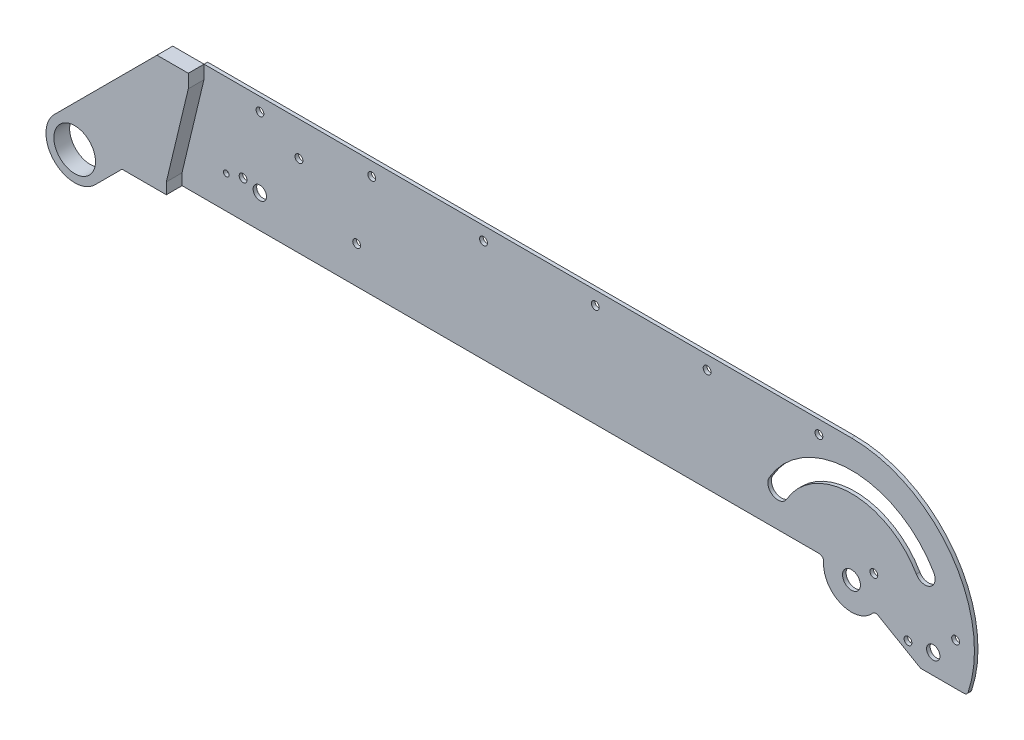
SolidWorks part; units mm, degrees
material "6061-T6 (SS)"
ref_plane "Front Plane" through (0, 0, 0) normal (0, 0, 1) x (1, 0, 0)
ref_plane "Top Plane" through (0, 0, 0) normal (0, 1, 0) x (1, 0, 0)
ref_plane "Right Plane" through (0, 0, 0) normal (1, 0, 0) x (0, 0, -1)
sketch "Sketch1" plane through (0, 0, 0) normal (0, 0, 1) x (1, 0, 0)
  line L0 (0, 0) -> (340.4001, 0) construction
  line L1 (340.4001, 0) -> (373.3091, 19) construction
  line L2 (340.4001, 0) -> (307.4911, 19) construction
  line L3 (340.4001, 0) -> (376.9688, -9.7841) construction
  line L5 (-50, -75) -> (450, -75)
  line L6 (-50, -75) -> (-50, 75)
  line L7 (-50, 75) -> (450, 75)
  line L8 (450, -75) -> (450, 75)
  circle A0 centre (0, 0) radius 9.3
  circle A1 centre (340.4001, 0) radius 4
  circle A2 centre (373.3091, 19) radius 4.5
  circle A3 centre (307.4911, 19) radius 4.5
  circle A4 centre (376.9688, -9.7841) radius 3
  circle A5 centre (340.4001, 0) radius 42.5
  circle A6 centre (340.4001, 0) radius 33.5
  dimension "D1" = 340.4001
  dimension "D2" = 36.5687
  dimension "D6" = 8
  dimension "D7" = 6
  dimension "D8" = 9
  dimension "D9" = 9
  dimension "D12" = 18.6
  dimension "D3" = 9.7841
  dimension "D4" = 150
  dimension "D5" = 120
  dimension "D10" = 38
  dimension "D11" = 38
  dimension "D13" = 150
  dimension "D14" = 500
  dimension "D15" = 75
  dimension "D16" = 50
extrude "Boss-Extrude1" add sketch "Sketch1" along normal blind 1.5875 contours L5 L8 L7 L6 A5 A0 | A6 A3 A5 A2 A4 | A6 A1 region at (189.2496, 0, 0) region at (377.7584, 20.1922, 0) region at (371.8434, 8.4252, 0)
sketch "Sketch3" plane through (0, 0, 1.5875) normal (0, 0, 1) x (1, 0, 0)
  line L0 (-50, 55) -> (450, 55)
  line L1 (340.4001, 0) -> (350.803, -6.9303) construction
  line L2 (-50, -75) -> (-50, 75) construction
  line L3 (450, -75) -> (450, 75) construction
  line L4 (-9.0863, 9.0863) -> (36.8274, 55)
  line L5 (0, 0) -> (-9.0863, 9.0863) construction
  line L6 (0, 0) -> (9.0863, -9.0863) construction
  line L7 (-50, 3) -> (450, 3) construction
  line L8 (9.0863, -9.0863) -> (21.1726, 3)
  line L9 (30.8962, 3) -> (328.2654, 3)
  line L10 (450, -18.7841) -> (-50, -18.7841) construction
  line L11 (350.803, -6.9303) -> (371.3324, -18.7841)
  line L12 (371.3324, -18.7841) -> (392.093, -18.7841)
  line L13 (21.1726, 3) -> (30.8962, 3)
  circle A0 centre (0, 0) radius 12.85
  circle A1 centre (376.9688, -9.7841) radius 3 construction
  circle A2 centre (340.4001, 0) radius 12.5
  circle A3 centre (340.4001, 0) radius 55
  line M7 (-50, -75) -> (450, -75)
  line M8 (450, -75) -> (450, 75)
  line M9 (450, 75) -> (-50, 75)
  line M10 (-50, 75) -> (-50, -75)
  dimension "D1" = 25.7
  dimension "D4" = 9
  dimension "D5" = 25
  dimension "D2" = 55
  dimension "D3" = 3
  dimension "D6" = 23.7059
  dimension "D7" = 149.998
  dimension "D8" = 45
  dimension "D10" = 180
extrude "Cut-Extrude1" cut sketch "Sketch3" against normal blind 7 contours A3 L9 A0 L4 L0 M10 M7 M8 | L9 A3 L12 L11 A2 | L0 M10 M8 M9 region at (200, 65, 1.5875) region at (185.623, -26.8332, 1.5875) region at (333.2112, -26.2581, 1.5875)
sketch "Sketch4" plane through (0, 0, 1.5875) normal (0, 0, 1) x (1, 0, 0)
  line L0 (0, 0) -> (55, 55) construction
  line L1 (36.8274, 55) -> (340.4001, 55) construction
  line L2 (50.8274, 49) -> (41, 8)
  line L3 (6.47, 24.6427) -> (23.1127, 8)
  line L4 (-9.0863, 9.0863) -> (36.8274, 55) construction
  line L5 (15.7908, 8) -> (84.2458, 8) construction
  line L6 (21.1726, 3) -> (328.2654, 3) construction
  line L7 (41, 3) -> (41, 8)
  line L8 (23.1127, 8) -> (41, 8)
  line L9 (50.8274, 55) -> (50.8274, 49)
  line L10 (50.8274, 49) -> (30.8274, 49)
  line L11 (50.8274, 55) -> (36.8274, 55)
  line L12 (36.8274, 55) -> (30.8274, 49)
  line L13 (41, 3) -> (21.1726, 3)
  line L14 (21.1726, 3) -> (9.0863, -9.0863)
  line L15 (6.47, 24.6427) -> (-9.0863, 9.0863)
  line L16 (6.47, 24.6427) -> (30.8274, 49)
  circle A1 centre (0, 0) radius 12.85
  line M7 (36.8274, 55) -> (-9.0863, 9.0863)
  arc M8 (-9.0863, 9.0863) -> (9.0863, -9.0863) centre (0, 0) ccw
  line M9 (9.0863, -9.0863) -> (21.1726, 3)
  line M10 (21.1726, 3) -> (328.2654, 3)
  line M15 (340.4001, 55) -> (36.8274, 55)
  circle M20 centre (0, 0) radius 9.3
  dimension "D1" = 22
  dimension "D2" = 5
  dimension "D3" = 41
  dimension "D4" = 23.5363
  dimension "D5" = 6
  dimension "D6" = 20
extrude "Cut-Extrude2" cut sketch "Sketch4" against normal blind 10 contours A1 L7 L8 L3 M9 M10 M7 | A1 M8 M20 | L10 L9 M15 M7 region at (42.2391, 51.8235, 1.5875) region at (15.8265, 9.8256, 1.5875) region at (4.7784, 11.5361, 1.5875)
fillet "Fillet1" radius 2 3 edges at (392.093, -18.7841, 0.7937) (328.2654, 3, 0.7937) (350.803, -6.9303, 0.7937)
sketch "Sketch5" plane through (0, 0, 1.5875) normal (0, 0, 1) x (1, 0, 0)
  line L0 (6.47, 24.6427) -> (129.4858, 24.6427) construction
  circle A0 centre (17.47, 19.6427) radius 1.75
  circle A1 centre (42.47, 39.6427) radius 1.75
  circle A2 centre (93.27, 39.6427) radius 1.75
  circle A3 centre (68.27, 19.6427) radius 1.75
  circle A4 centre (119.07, 19.6427) radius 1.75
  circle A5 centre (75.77, 17.6427) radius 3
  circle A6 centre (60.77, 17.6427) radius 1.25
  dimension "D1" = 3.5
  dimension "D4" = 3.5
  dimension "D8" = 3.5
  dimension "D9" = 3.5
  dimension "D12" = 3.5
  dimension "D16" = 6
  dimension "D17" = 2.5
  dimension "D2" = 5
  dimension "D3" = 11
  dimension "D5" = 15
  dimension "D6" = 36
  dimension "D7" = 50.8
  dimension "D10" = 50.8
  dimension "D11" = 50.8
  dimension "D13" = 15
  dimension "D14" = 5
  dimension "D15" = 5
  dimension "D18" = 2
  dimension "D19" = 7.5
  dimension "D20" = 7.5
  dimension "D21" = 2
extrude "Cut-Extrude3" cut sketch "Sketch5" against normal blind 10
sketch "Sketch6" plane through (0, 0, 1.5875) normal (0, 0, 1) x (1, 0, 0)
  line L0 (340.4001, 0) -> (395.4001, 0) construction
  line L1 (350.4001, 7.5) -> (386.9688, 0) construction
  line L2 (386.9688, 0) -> (368.6844, 3.75) construction
  line L3 (368.6844, 3.75) -> (364.8326, -15.0311) construction
  line L4 (352.3209, -7.8068) -> (371.3324, -18.7841) construction
  circle A0 centre (340.4001, 0) radius 4
  arc A1 (392.5694, -17.4175) -> (340.4001, 55) centre (340.4001, 0) ccw construction
  circle A2 centre (376.9688, -9.7841) radius 3
  circle A3 centre (350.4001, 7.5) radius 1.75
  circle A4 centre (386.9688, 0) radius 1.75
  circle A5 centre (365.6708, -10.9441) radius 1.75
  dimension "D4" = 3.5
  dimension "D5" = 3.5
  dimension "D6" = 3.5
  dimension "D1" = 10
  dimension "D2" = 10
  dimension "D3" = 7.5
  dimension "D7" = 15
extrude "Cut-Extrude4" cut sketch "Sketch6" against normal blind 10
sketch "Sketch7" plane through (0, 0, 1.5875) normal (0, 0, 1) x (1, 0, 0)
  line L0 (50.8274, 49) -> (340.6, 49) construction
  line L1 (50.8274, 55) -> (50.8274, 49) construction
  circle A0 centre (75.8274, 49) radius 1.75
  circle A1 centre (125.8274, 49) radius 1.75
  circle A2 centre (175.8274, 49) radius 1.75
  circle A3 centre (225.8274, 49) radius 1.75
  circle A4 centre (275.8274, 49) radius 1.75
  circle A5 centre (325.8274, 49) radius 1.75
  dimension "D1" = 3.5
  dimension "D2" = 3.5
  dimension "D3" = 3.5
  dimension "D4" = 3.5
  dimension "D5" = 3.5
  dimension "D6" = 3.5
  dimension "D7" = 25
  dimension "D8" = 50
  dimension "D9" = 50
  dimension "D10" = 50
  dimension "D11" = 50
  dimension "D12" = 50
extrude "Cut-Extrude5" cut sketch "Sketch7" against normal blind 246.38
extrude "Boss-Extrude2" add sketch "Sketch4<5>" along normal blind 7.045 contours L10 L9 M15 M7 | A1 L7 L8 L3 M9 M10 M7 | A1 M8 M20 region at (42.2391, 51.8235, 1.5875) region at (15.8265, 9.8256, 1.5875) region at (4.7784, 11.5361, 1.5875)
sketch "Sketch4<5>" plane through (0, 0, 1.5875) normal (0, 0, 1) x (1, 0, 0) same geometry as "Sketch4"
sketch "Sketch9" plane through (0, 0, 8.6325) normal (0, 0, 1) x (1, 0, 0)
  line L0 (50.8274, 49) -> (41, 8)
  line L10 (371.3324, -18.7841) -> (390.6723, -18.7841)
  line L11 (340.4001, 55) -> (50.8274, 55)
  line L12 (50.8274, 55) -> (50.8274, 49)
  line L13 (50.8274, 49) -> (30.8274, 49)
  line L14 (30.8274, 49) -> (6.47, 24.6427)
  line L15 (6.47, 24.6427) -> (23.1127, 8)
  line L16 (23.1127, 8) -> (41, 8)
  line L17 (41, 8) -> (41, 3)
  line L18 (41, 3) -> (325.9346, 3)
  line L19 (352.3209, -7.8068) -> (371.3324, -18.7841)
  line L20 (371.3324, -18.7841) -> (390.6723, -18.7841)
  line L21 (340.4001, 55) -> (50.8274, 55)
  line L22 (50.8274, 55) -> (50.8274, 49)
  line L23 (50.8274, 49) -> (30.8274, 49)
  line L24 (30.8274, 49) -> (6.47, 24.6427)
  line L25 (6.47, 24.6427) -> (23.1127, 8)
  line L26 (23.1127, 8) -> (41, 8)
  line L27 (41, 8) -> (41, 3)
  line L28 (41, 3) -> (325.9346, 3)
  line L29 (352.3209, -7.8068) -> (371.3324, -18.7841)
  arc A5 (390.6723, -18.7841) -> (392.5694, -17.4175) centre (390.6723, -16.7841) ccw
  arc A6 (392.5694, -17.4175) -> (340.4001, 55) centre (340.4001, 0) ccw
  arc A7 (327.9299, 0.8621) -> (325.9346, 3) centre (325.9346, 1) ccw
  arc A8 (327.9299, 0.8621) -> (349.8145, -8.2231) centre (340.4001, 0) ccw
  arc A9 (352.3209, -7.8068) -> (349.8145, -8.2231) centre (351.3208, -9.5388) ccw
  arc A10 (390.6723, -18.7841) -> (392.5694, -17.4175) centre (390.6723, -16.7841) ccw
  arc A11 (392.5694, -17.4175) -> (340.4001, 55) centre (340.4001, 0) ccw
  arc A12 (327.9299, 0.8621) -> (325.9346, 3) centre (325.9346, 1) ccw
  arc A13 (327.9299, 0.8621) -> (349.8145, -8.2231) centre (340.4001, 0) ccw
  arc A14 (352.3209, -7.8068) -> (349.8145, -8.2231) centre (351.3208, -9.5388) ccw
  line M21 (41, 8) -> (23.1127, 8)
  line M22 (23.1127, 8) -> (6.47, 24.6427)
  dimension "D1" = 0
extrude "Boss-Extrude9" add sketch "Sketch9" against normal blind 7 contours L23 L24 L0 M22 M21 region at (30.9038, 28.3094, 8.6325)
